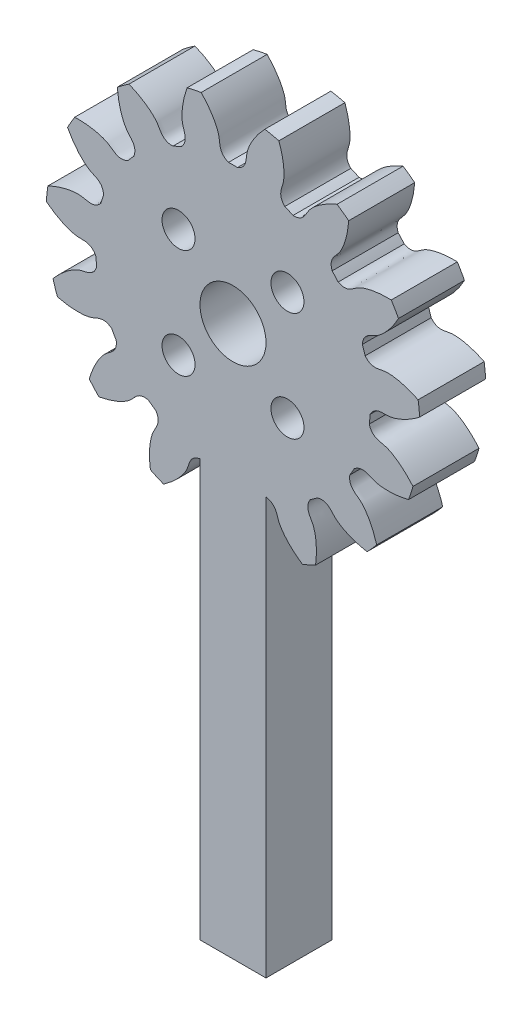
SolidWorks part; units mm, degrees
ref_plane "前视基准面" through (0, 0, 0) normal (0, 0, 1) x (1, 0, 0)
ref_plane "上视基准面" through (0, 0, 0) normal (0, 1, 0) x (1, 0, 0)
ref_plane "右视基准面" through (0, 0, 0) normal (1, 0, 0) x (0, 0, -1)
sketch "草图1" plane through (0, 0, 0) normal (0, 0, 1) x (1, 0, 0)
  circle A0 centre (0, 0) radius 17
extrude "凸台-拉伸1" add sketch "草图1" along normal blind 30
ref_axis "基准轴1" through (0, 0, -1.5) along (0, 0, 1)
sketch "草图2" plane through (0, 0, 0) normal (0, 0, 1) x (1, 0, 0)
  line L0 (0, 0) -> (0, 17) construction
  circle A0 centre (0, 0) radius 17 construction
  arc A1 (0.4086, 12.4933) -> (-0.4086, 12.4933) centre (0, 0) ccw
  arc A2 (6.4937, 19.2719) -> (-6.4937, 19.2719) centre (0, 0) ccw
  spline S0 degree 3 poles (0.4086, 12.4933) (1.3144, 12.8688) (1.1442, 13.5727) (1.3025, 14.217) (1.3149, 14.2633) (1.3297, 14.3148) (1.3472, 14.3713) (1.3676, 14.4329) (1.3912, 14.4993) (1.418, 14.5705) (1.4484, 14.6465) (1.4824, 14.7269) (1.5204, 14.8119) (1.5624, 14.9011) (1.6088, 14.9946) (1.6596, 15.0921) (1.715, 15.1935) (1.7753, 15.2987) (1.8405, 15.4075) (1.9109, 15.5198) (1.9867, 15.6353) (2.0679, 15.754) (2.1547, 15.8755) (2.2473, 15.9999) (2.3459, 16.1268) (2.4505, 16.2561) (2.5613, 16.3877) (2.6784, 16.5212) (2.802, 16.6565) (2.9322, 16.7934) (3.069, 16.9316) (3.2126, 17.0711) (3.3631, 17.2115) (3.5206, 17.3526) (3.6851, 17.4942) (3.8568, 17.6361) (4.0357, 17.778) (4.2219, 17.9197) (4.4154, 18.061) (4.6163, 18.2017) (4.8247, 18.3414) (5.0406, 18.48) (5.2641, 18.6172) (5.4951, 18.7527) (5.7336, 18.8864) (6.0652, 19.0635) (6.3203, 19.1901) (6.4937, 19.2719) knots 0 0 0 0 0.202473 0.206979 0.212085 0.217793 0.224101 0.23101 0.23852 0.24663 0.255341 0.264653 0.274566 0.285079 0.296194 0.307909 0.320225 0.333141 0.346659 0.360777 0.375496 0.390816 0.406736 0.423257 0.440379 0.458102 0.476426 0.49535 0.514875 0.535001 0.555728 0.577055 0.598984 0.621513 0.644642 0.668373 0.692704 0.717636 0.743169 0.769303 0.796037 0.823373 0.851309 0.879845 0.908983 0.938721 1 1 1 1
  spline S1 degree 3 poles (-0.4086, 12.4933) (-1.3144, 12.8688) (-1.1442, 13.5727) (-1.3025, 14.217) (-1.3149, 14.2633) (-1.3297, 14.3148) (-1.3472, 14.3713) (-1.3676, 14.4329) (-1.3912, 14.4993) (-1.418, 14.5705) (-1.4484, 14.6465) (-1.4824, 14.7269) (-1.5204, 14.8119) (-1.5624, 14.9011) (-1.6088, 14.9946) (-1.6596, 15.0921) (-1.715, 15.1935) (-1.7753, 15.2987) (-1.8405, 15.4075) (-1.9109, 15.5198) (-1.9867, 15.6353) (-2.0679, 15.754) (-2.1547, 15.8755) (-2.2473, 15.9999) (-2.3459, 16.1268) (-2.4505, 16.2561) (-2.5613, 16.3877) (-2.6784, 16.5212) (-2.802, 16.6565) (-2.9322, 16.7934) (-3.069, 16.9316) (-3.2126, 17.0711) (-3.3631, 17.2115) (-3.5206, 17.3526) (-3.6851, 17.4942) (-3.8568, 17.6361) (-4.0357, 17.778) (-4.2219, 17.9197) (-4.4154, 18.061) (-4.6163, 18.2017) (-4.8247, 18.3414) (-5.0406, 18.48) (-5.2641, 18.6172) (-5.4951, 18.7527) (-5.7336, 18.8864) (-6.0652, 19.0635) (-6.3203, 19.1901) (-6.4937, 19.2719) knots 0 0 0 0 0.202473 0.206979 0.212085 0.217793 0.224101 0.23101 0.23852 0.24663 0.255341 0.264653 0.274566 0.285079 0.296194 0.307909 0.320225 0.333141 0.346659 0.360777 0.375496 0.390816 0.406736 0.423257 0.440379 0.458102 0.476426 0.49535 0.514875 0.535001 0.555728 0.577055 0.598984 0.621513 0.644642 0.668373 0.692704 0.717636 0.743169 0.769303 0.796037 0.823373 0.851309 0.879845 0.908983 0.938721 1 1 1 1
extrude "切除-拉伸1" cut sketch "草图2" along normal through all
pattern_circular "阵列(圆周)1" count 15 every 24 about axis through (0, 0, -1.5) along (0, 0, 1) of "切除-拉伸1"
sketch "草图3" plane through (0, 0, 0) normal (0, 0, 1) x (1, 0, 0)
  circle A0 centre (0, 0) radius 15 construction
  dimension "Dn" = 30
sketch "草图4" plane through (0, 0, 30) normal (0, 0, 1) x (1, 0, 0)
  arc A30 (-4.7082, 11.5794) -> (-5.4547, 11.247) centre (0, 0) ccw
  arc A31 (-9.4567, 14.127) -> (-10.5132, 13.3593) centre (0, 0) ccw
  arc A32 (-9.011, 8.6633) -> (-9.5577, 8.056) centre (0, 0) ccw
  arc A33 (-14.3851, 9.0592) -> (-15.0381, 7.9282) centre (0, 0) ccw
  arc A34 (-11.7556, 4.2492) -> (-12.0081, 3.4721) centre (0, 0) ccw
  arc A35 (-16.8261, 2.4251) -> (-16.9627, 1.1263) centre (0, 0) ccw
  arc A36 (-12.4676, -0.8996) -> (-12.3822, -1.7122) centre (0, 0) ccw
  arc A37 (-16.3578, -4.6284) -> (-15.9542, -5.8704) centre (0, 0) ccw
  arc A38 (-11.0238, -5.8928) -> (-10.6152, -6.6005) centre (0, 0) ccw
  arc A39 (-13.0611, -10.8816) -> (-12.1872, -11.8521) centre (0, 0) ccw
  arc A40 (-7.6739, -9.8672) -> (-7.0128, -10.3475) centre (0, 0) ccw
  arc A41 (-7.5059, -15.2532) -> (-6.3129, -15.7844) centre (0, 0) ccw
  arc A42 (-2.9971, -12.1354) -> (-2.1979, -12.3053) centre (0, 0) ccw
  arc A43 (-0.653, -16.9875) -> (0.653, -16.9875) centre (0, 0) ccw
  arc A44 (2.1979, -12.3053) -> (2.9971, -12.1354) centre (0, 0) ccw
  arc A45 (6.3129, -15.7844) -> (7.5059, -15.2532) centre (0, 0) ccw
  arc A46 (7.0128, -10.3475) -> (7.6739, -9.8672) centre (0, 0) ccw
  arc A47 (12.1872, -11.8521) -> (13.0611, -10.8816) centre (0, 0) ccw
  arc A48 (10.6152, -6.6005) -> (11.0238, -5.8928) centre (0, 0) ccw
  arc A49 (15.9542, -5.8704) -> (16.3578, -4.6284) centre (0, 0) ccw
  arc A50 (12.3822, -1.7122) -> (12.4676, -0.8996) centre (0, 0) ccw
  arc A51 (16.9627, 1.1263) -> (16.8261, 2.4251) centre (0, 0) ccw
  arc A52 (12.0081, 3.4721) -> (11.7556, 4.2492) centre (0, 0) ccw
  arc A53 (15.0381, 7.9282) -> (14.3851, 9.0592) centre (0, 0) ccw
  arc A54 (9.5577, 8.056) -> (9.011, 8.6633) centre (0, 0) ccw
  arc A55 (10.5132, 13.3593) -> (9.4567, 14.127) centre (0, 0) ccw
  arc A56 (5.4547, 11.247) -> (4.7082, 11.5794) centre (0, 0) ccw
  arc A57 (4.1706, 16.4805) -> (2.8932, 16.752) centre (0, 0) ccw
  arc A58 (0.4086, 12.4933) -> (-0.4086, 12.4933) centre (0, 0) ccw
  arc A59 (-2.8932, 16.752) -> (-4.1706, 16.4805) centre (0, 0) ccw
  arc A60 (-4.7082, 11.5794) -> (-5.4547, 11.247) centre (0, 0) ccw
  arc A61 (-9.4567, 14.127) -> (-10.5132, 13.3593) centre (0, 0) ccw
  arc A62 (-9.011, 8.6633) -> (-9.5577, 8.056) centre (0, 0) ccw
  arc A63 (-14.3851, 9.0592) -> (-15.0381, 7.9282) centre (0, 0) ccw
  arc A64 (-11.7556, 4.2492) -> (-12.0081, 3.4721) centre (0, 0) ccw
  arc A65 (-16.8261, 2.4251) -> (-16.9627, 1.1263) centre (0, 0) ccw
  arc A66 (-12.4676, -0.8996) -> (-12.3822, -1.7122) centre (0, 0) ccw
  arc A67 (-16.3578, -4.6284) -> (-15.9542, -5.8704) centre (0, 0) ccw
  arc A68 (-11.0238, -5.8928) -> (-10.6152, -6.6005) centre (0, 0) ccw
  arc A69 (-13.0611, -10.8816) -> (-12.1872, -11.8521) centre (0, 0) ccw
  arc A70 (-7.6739, -9.8672) -> (-7.0128, -10.3475) centre (0, 0) ccw
  arc A71 (-7.5059, -15.2532) -> (-6.3129, -15.7844) centre (0, 0) ccw
  arc A72 (-2.9971, -12.1354) -> (-2.1979, -12.3053) centre (0, 0) ccw
  arc A73 (-0.653, -16.9875) -> (0.653, -16.9875) centre (0, 0) ccw
  arc A74 (2.1979, -12.3053) -> (2.9971, -12.1354) centre (0, 0) ccw
  arc A75 (6.3129, -15.7844) -> (7.5059, -15.2532) centre (0, 0) ccw
  arc A76 (7.0128, -10.3475) -> (7.6739, -9.8672) centre (0, 0) ccw
  arc A77 (12.1872, -11.8521) -> (13.0611, -10.8816) centre (0, 0) ccw
  arc A78 (10.6152, -6.6005) -> (11.0238, -5.8928) centre (0, 0) ccw
  arc A79 (15.9542, -5.8704) -> (16.3578, -4.6284) centre (0, 0) ccw
  arc A80 (12.3822, -1.7122) -> (12.4676, -0.8996) centre (0, 0) ccw
  arc A81 (16.9627, 1.1263) -> (16.8261, 2.4251) centre (0, 0) ccw
  arc A82 (12.0081, 3.4721) -> (11.7556, 4.2492) centre (0, 0) ccw
  arc A83 (15.0381, 7.9282) -> (14.3851, 9.0592) centre (0, 0) ccw
  arc A84 (9.5577, 8.056) -> (9.011, 8.6633) centre (0, 0) ccw
  arc A85 (10.5132, 13.3593) -> (9.4567, 14.127) centre (0, 0) ccw
  arc A86 (5.4547, 11.247) -> (4.7082, 11.5794) centre (0, 0) ccw
  arc A87 (4.1706, 16.4805) -> (2.8932, 16.752) centre (0, 0) ccw
  arc A88 (0.4086, 12.4933) -> (-0.4086, 12.4933) centre (0, 0) ccw
  arc A89 (-2.8932, 16.752) -> (-4.1706, 16.4805) centre (0, 0) ccw
  spline S30 degree 3 poles (3089.1595, 2545.0128) (-48.0651, -41.2526) (-1.4026, 5.2781) (-6.9834, 12.4722) (-7.0266, 12.5244) (-7.0761, 12.5809) (-7.1369, 12.6476) (-7.2252, 12.7386) (-7.3478, 12.8552) (-7.4919, 12.9818) (-7.6584, 13.1167) (-7.8482, 13.2583) (-8.0622, 13.405) (-8.3009, 13.555) (-8.565, 13.7067) (-8.8549, 13.858) (-42.0056, 29.516) (-165.8302, -157.3856) (3462.6996, 1998.8009) knots -2.221696 -2.221696 -2.221696 -2.221696 0.673329 0.677835 0.688649 0.694957 0.701866 0.717486 0.735509 0.755935 0.778765 0.803997 0.831633 0.861672 0.894113 0.928958 0.966206 12.611489 12.611489 12.611489 12.611489 only from (-5.4547, 11.247) to (-9.4567, 14.127)
  spline S31 degree 3 poles (-2967.0957, -2679.8675) (198.3354, 111.6925) (-15.6965, 48.1718) (-10.4174, 12.5396) (-10.3587, 12.2293) (-10.2927, 11.9436) (-10.2213, 11.6825) (-10.1464, 11.4459) (-10.0697, 11.2338) (-10.0041, 11.0727) (-9.9413, 10.931) (-9.8926, 10.8293) (-9.8442, 10.7358) (-9.8106, 10.6738) (-9.7785, 10.6175) (-9.74, 10.5529) (-9.7038, 10.4958) (-4.5863, 2.965) (54.0858, 32.9645) (-3374.9897, -2151.4722) knots -11.389987 -11.389987 -11.389987 -11.389987 0.052718 0.088765 0.122408 0.153648 0.182485 0.208919 0.23295 0.254578 0.264491 0.282514 0.290624 0.298134 0.305043 0.311351 0.322165 0.326671 3.221678 3.221678 3.221678 3.221678 only from (-10.5132, 13.3593) to (-9.011, 8.6633)
  spline S32 degree 3 poles (1786.9376, 3581.4592) (-27.1307, -57.236) (-3.4282, 4.2513) (-11.4526, 8.5535) (-11.5132, 8.5836) (-11.5815, 8.6151) (-11.6641, 8.6513) (-11.7819, 8.6985) (-11.9413, 8.7552) (-12.1243, 8.8122) (-12.3313, 8.8677) (-12.5623, 8.9199) (-12.8175, 8.9669) (-13.0966, 9.0069) (-13.3995, 9.038) (-13.7259, 9.0583) (-50.3793, 9.879) (-87.479, -211.2281) (2350.348, 3234.4023) knots -2.221696 -2.221696 -2.221696 -2.221696 0.673329 0.677835 0.688649 0.694957 0.701866 0.717486 0.735509 0.755935 0.778765 0.803997 0.831633 0.861672 0.894113 0.928958 0.966206 12.611489 12.611489 12.611489 12.611489 only from (-9.5577, 8.056) to (-14.3851, 9.0592)
  spline S33 degree 3 poles (-1620.5765, -3655.0073) (135.759, 182.7064) (-33.9327, 37.6228) (-14.6171, 7.2183) (-14.4372, 6.9587) (-14.2607, 6.7246) (-14.0893, 6.5151) (-13.9246, 6.3295) (-13.7683, 6.1669) (-13.6429, 6.0464) (-13.5278, 5.9425) (-13.442, 5.8694) (-13.3598, 5.8036) (-13.3039, 5.7607) (-13.2516, 5.7223) (-13.1902, 5.6789) (-13.1339, 5.6415) (-5.3958, 0.8433) (36.002, 52.1132) (-2208.1239, -3338.1997) knots -11.389987 -11.389987 -11.389987 -11.389987 0.052718 0.088765 0.122408 0.153648 0.182485 0.208919 0.23295 0.254578 0.264491 0.282514 0.290624 0.298134 0.305043 0.311351 0.322165 0.326671 3.221678 3.221678 3.221678 3.221678 only from (-15.0381, 7.9282) to (-11.7556, 4.2492)
  spline S34 degree 3 poles (175.7381, 3998.6388) (-1.5051, -63.3227) (-4.8609, 2.4894) (-13.9415, 3.1558) (-14.0091, 3.1587) (-14.0843, 3.1597) (-14.1745, 3.1591) (-14.3013, 3.1544) (-14.47, 3.1414) (-14.6604, 3.119) (-14.872, 3.0855) (-15.1043, 3.0392) (-15.3565, 2.9783) (-15.6277, 2.9013) (-15.9171, 2.8065) (-16.2236, 2.6924) (-50.0419, -11.4661) (5.9982, -228.5474) (831.5998, 3910.7461) knots -2.221696 -2.221696 -2.221696 -2.221696 0.673329 0.677835 0.688649 0.694957 0.701866 0.717486 0.735509 0.755935 0.778765 0.803997 0.831633 0.861672 0.894113 0.928958 0.966206 12.611489 12.611489 12.611489 12.611489 only from (-12.0081, 3.4721) to (-16.8261, 2.4251)
  spline S35 degree 3 poles (6.1551, -3998.1632) (49.7086, 222.1288) (-46.3016, 20.5684) (-16.2893, 0.649) (-16.0194, 0.485) (-15.763, 0.3428) (-15.5212, 0.2212) (-15.2952, 0.1186) (-15.0863, 0.0336) (-14.9227, -0.0254) (-14.7753, -0.0735) (-14.6671, -0.1054) (-14.5653, -0.132) (-14.4968, -0.1485) (-14.4334, -0.1624) (-14.3597, -0.177) (-14.293, -0.1883) (-5.2723, -1.4243) (11.6931, 62.2511) (-659.4535, -3947.7221) knots -11.389987 -11.389987 -11.389987 -11.389987 0.052718 0.088765 0.122408 0.153648 0.182485 0.208919 0.23295 0.254578 0.264491 0.282514 0.290624 0.298134 0.305043 0.311351 0.322165 0.326671 3.221678 3.221678 3.221678 3.221678 only from (-16.9627, 1.1263) to (-12.4676, -0.8996)
  spline S36 degree 3 poles (-1465.8482, 3724.4174) (24.3807, -58.4604) (-5.4532, 0.297) (-14.0198, -2.7875) (-14.0827, -2.8124) (-14.1518, -2.8421) (-14.234, -2.8793) (-14.3479, -2.9352) (-14.4967, -3.0157) (-14.6615, -3.1136) (-14.8413, -3.2303) (-15.0346, -3.3671) (-15.2402, -3.5252) (-15.4567, -3.7059) (-15.6825, -3.9102) (-15.9161, -4.1391) (-41.0519, -30.8287) (98.4382, -206.3487) (-830.9396, 3910.8865) knots -2.221696 -2.221696 -2.221696 -2.221696 0.673329 0.677835 0.688649 0.694957 0.701866 0.717486 0.735509 0.755935 0.778765 0.803997 0.831633 0.861672 0.894113 0.928958 0.966206 12.611489 12.611489 12.611489 12.611489 only from (-12.3822, -1.7122) to (-16.3578, -4.6284)
  spline S37 degree 3 poles (1631.8224, -3650.0003) (-44.9369, 223.143) (-50.6646, -0.0424) (-15.145, -6.0326) (-14.8318, -6.0726) (-14.5396, -6.0982) (-14.2692, -6.111) (-14.0211, -6.1128) (-13.7957, -6.1054) (-13.6222, -6.0928) (-13.468, -6.0768) (-13.3562, -6.062) (-13.2524, -6.0449) (-13.1831, -6.032) (-13.1196, -6.0189) (-13.0462, -6.0023) (-12.9807, -5.9855) (-4.2372, -3.4456) (-14.6376, 61.6252) (1003.2425, -3874.6475) knots -11.389987 -11.389987 -11.389987 -11.389987 0.052718 0.088765 0.122408 0.153648 0.182485 0.208919 0.23295 0.254578 0.264491 0.282514 0.290624 0.298134 0.305043 0.311351 0.322165 0.326671 3.221678 3.221678 3.221678 3.221678 only from (-15.9542, -5.8704) to (-11.0238, -5.8928)
  spline S38 degree 3 poles (-2853.976, 2806.2104) (46.0508, -43.4897) (-5.1025, -1.9467) (-11.6739, -8.2489) (-11.7213, -8.2972) (-11.7723, -8.3524) (-11.8323, -8.4198) (-11.9136, -8.5172) (-12.0168, -8.6513) (-12.1276, -8.8078) (-12.2443, -8.9875) (-12.3653, -9.1911) (-12.4888, -9.4192) (-12.6131, -9.6723) (-12.7363, -9.9508) (-12.8565, -10.255) (-24.9636, -44.8607) (173.8574, -148.4705) (-2349.8019, 3234.799) knots -2.221696 -2.221696 -2.221696 -2.221696 0.673329 0.677835 0.688649 0.694957 0.701866 0.717486 0.735509 0.755935 0.778765 0.803997 0.831633 0.861672 0.894113 0.928958 0.966206 12.611489 12.611489 12.611489 12.611489 only from (-10.6152, -6.6005) to (-13.0611, -10.8816)
  spline S39 degree 3 poles (2975.3328, -2670.7192) (-131.8123, 185.5738) (-46.2672, -20.6458) (-11.382, -11.6711) (-11.0795, -11.5803) (-10.8023, -11.4848) (-10.5501, -11.3865) (-10.3226, -11.2872) (-10.1197, -11.1888) (-9.9664, -11.1067) (-9.832, -11.0294) (-9.7359, -10.9703) (-9.648, -10.9125) (-9.5899, -10.8726) (-9.5372, -10.8348) (-9.477, -10.7898) (-9.4239, -10.7477) (-2.4694, -4.8712) (-38.4374, 50.3438) (2492.4687, -3131.6111) knots -11.389987 -11.389987 -11.389987 -11.389987 0.052718 0.088765 0.122408 0.153648 0.182485 0.208919 0.23295 0.254578 0.264491 0.282514 0.290624 0.298134 0.305043 0.311351 0.322165 0.326671 3.221678 3.221678 3.221678 3.221678 only from (-12.1872, -11.8521) to (-7.6739, -9.8672)
  spline S40 degree 3 poles (-3748.6254, 1402.7842) (59.7584, -20.9993) (-3.8696, -3.8538) (-7.3095, -12.2839) (-7.3331, -12.3474) (-7.3573, -12.4185) (-7.3847, -12.5045) (-7.4193, -12.6266) (-7.4591, -12.791) (-7.4966, -12.979) (-7.5302, -13.1907) (-7.5579, -13.4259) (-7.578, -13.6845) (-7.5886, -13.9663) (-7.5878, -14.2708) (-7.574, -14.5976) (-4.5589, -51.1359) (219.215, -64.9204) (-3462.3621, 1999.3854) knots -2.221696 -2.221696 -2.221696 -2.221696 0.673329 0.677835 0.688649 0.694957 0.701866 0.717486 0.735509 0.755935 0.778765 0.803997 0.831633 0.861672 0.894113 0.928958 0.966206 12.611489 12.611489 12.611489 12.611489 only from (-7.0128, -10.3475) to (-7.5059, -15.2532)
  spline S41 degree 3 poles (3804.3812, -1229.6465) (-195.8962, 115.9172) (-33.8697, -37.6795) (-5.6509, -15.2915) (-5.4115, -15.0855) (-5.1971, -14.8855) (-5.0067, -14.6931) (-4.8393, -14.51) (-4.6939, -14.3375) (-4.5872, -14.2002) (-4.4959, -14.0749) (-4.4321, -13.9819) (-4.3754, -13.8932) (-4.3385, -13.8331) (-4.3057, -13.7772) (-4.2691, -13.7116) (-4.2377, -13.6516) (-0.2746, -5.4544) (-55.591, 30.3574) (3550.7245, -1847.0907) knots -11.389987 -11.389987 -11.389987 -11.389987 0.052718 0.088765 0.122408 0.153648 0.182485 0.208919 0.23295 0.254578 0.264491 0.282514 0.290624 0.298134 0.305043 0.311351 0.322165 0.326671 3.221678 3.221678 3.221678 3.221678 only from (-6.3129, -15.7844) to (-2.9971, -12.1354)
  spline S42 degree 3 poles (-3995.1035, -243.1962) (63.1332, 5.1221) (-1.9676, -5.0945) (-1.6813, -14.195) (-1.677, -14.2625) (-1.6702, -14.3374) (-1.6602, -14.4271) (-1.6422, -14.5527) (-1.6116, -14.719) (-1.5695, -14.9061) (-1.514, -15.1131) (-1.4437, -15.3393) (-1.3568, -15.5837) (-1.2519, -15.8454) (-1.1274, -16.1233) (-0.9818, -16.4162) (16.6341, -48.5692) (226.6684, 29.855) (-3976.2485, 418.2599) knots -2.221696 -2.221696 -2.221696 -2.221696 0.673329 0.677835 0.688649 0.694957 0.701866 0.717486 0.735509 0.755935 0.778765 0.803997 0.831633 0.861672 0.894113 0.928958 0.966206 12.611489 12.611489 12.611489 12.611489 only from (-2.1979, -12.3053) to (-0.653, -16.9875)
  spline S43 degree 3 poles (3975.6174, 424.0432) (-226.1079, 26.2175) (-15.6159, -48.198) (1.0573, -16.2679) (1.1922, -15.9824) (1.3067, -15.7124) (1.4024, -15.4592) (1.4808, -15.2238) (1.5435, -15.0071) (1.5851, -14.8383) (1.6176, -14.6867) (1.638, -14.5758) (1.6538, -14.4717) (1.663, -14.4018) (1.6702, -14.3374) (1.677, -14.2625) (1.6813, -14.195) (1.9676, -5.0946) (-63.1324, 5.122) (3995.0277, -243.1916) knots -11.389987 -11.389987 -11.389987 -11.389987 0.052718 0.088765 0.122408 0.153648 0.182485 0.208919 0.23295 0.254578 0.264491 0.282514 0.290624 0.298134 0.305043 0.311351 0.322165 0.326671 3.221678 3.221678 3.221678 3.221678 only from (0.653, -16.9875) to (2.1979, -12.3053)
  spline S44 degree 3 poles (-3550.7918, -1847.1258) (55.5917, 30.3579) (0.2746, -5.4544) (4.2377, -13.6516) (4.2691, -13.7116) (4.3057, -13.7772) (4.3513, -13.855) (4.4189, -13.9625) (4.5145, -14.102) (4.6291, -14.2557) (4.7639, -14.4223) (4.9202, -14.6003) (5.0989, -14.7883) (5.3012, -14.9847) (5.528, -15.1879) (5.7802, -15.3963) (34.9509, -37.6045) (194.9288, 119.4683) (-3802.6054, -1235.1865) knots -2.221696 -2.221696 -2.221696 -2.221696 0.673329 0.677835 0.688649 0.694957 0.701866 0.717486 0.735509 0.755935 0.778765 0.803997 0.831633 0.861672 0.894113 0.928958 0.966206 12.611489 12.611489 12.611489 12.611489 only from (2.9971, -12.1354) to (6.3129, -15.7844)
  spline S45 degree 3 poles (3459.4333, 2004.4121) (-217.2235, -68.0155) (5.338, -50.3826) (7.5826, -14.4315) (7.5897, -14.1157) (7.5846, -13.8225) (7.569, -13.5523) (7.5449, -13.3054) (7.514, -13.0819) (7.4834, -12.9107) (7.4513, -12.759) (7.4249, -12.6494) (7.397, -12.5479) (7.377, -12.4803) (7.3573, -12.4185) (7.3331, -12.3474) (7.3095, -12.2839) (3.8697, -3.8538) (-59.7576, -20.999) (3748.5543, 1402.7576) knots -11.389987 -11.389987 -11.389987 -11.389987 0.052718 0.088765 0.122408 0.153648 0.182485 0.208919 0.23295 0.254578 0.264491 0.282514 0.290624 0.298134 0.305043 0.311351 0.322165 0.326671 3.221678 3.221678 3.221678 3.221678 only from (7.5059, -15.2532) to (7.0128, -10.3475)
  spline S46 degree 3 poles (-2492.516, -3131.6705) (38.4378, 50.3445) (2.4694, -4.8711) (9.4239, -10.7477) (9.477, -10.7898) (9.5372, -10.8348) (9.6105, -10.8873) (9.7159, -10.958) (9.86, -11.0466) (10.0272, -11.1405) (10.2181, -11.2378) (10.4333, -11.3368) (10.673, -11.4358) (10.9377, -11.533) (11.2276, -11.6264) (11.5427, -11.7142) (47.2244, -20.1376) (129.4842, 188.4244) (-2971.4573, -2675.058) knots -2.221696 -2.221696 -2.221696 -2.221696 0.673329 0.677835 0.688649 0.694957 0.701866 0.717486 0.735509 0.755935 0.778765 0.803997 0.831633 0.861672 0.894113 0.928958 0.966206 12.611489 12.611489 12.611489 12.611489 only from (7.6739, -9.8672) to (12.1872, -11.8521)
  spline S47 degree 3 poles (2345.0818, 3238.1998) (-170.7791, -150.488) (25.369, -43.8556) (12.7969, -10.0997) (12.6749, -9.8084) (12.551, -9.5426) (12.4269, -9.302) (12.3044, -9.0863) (12.1853, -8.8947) (12.0877, -8.7508) (11.9967, -8.6252) (11.9279, -8.5358) (11.8612, -8.4545) (11.8154, -8.4009) (11.7723, -8.3524) (11.7213, -8.2972) (11.6739, -8.2489) (5.1026, -1.9467) (-46.0502, -43.4892) (2853.9219, 2806.1572) knots -11.389987 -11.389987 -11.389987 -11.389987 0.052718 0.088765 0.122408 0.153648 0.182485 0.208919 0.23295 0.254578 0.264491 0.282514 0.290624 0.298134 0.305043 0.311351 0.322165 0.326671 3.221678 3.221678 3.221678 3.221678 only from (13.0611, -10.8816) to (10.6152, -6.6005)
  spline S48 degree 3 poles (-1003.2615, -3874.721) (14.6378, 61.626) (4.2371, -3.4456) (12.9807, -5.9855) (13.0462, -6.0023) (13.1196, -6.0189) (13.2079, -6.0371) (13.3329, -6.0589) (13.5006, -6.0812) (13.6915, -6.0989) (13.9055, -6.1101) (14.1424, -6.1131) (14.4017, -6.106) (14.683, -6.0871) (14.9858, -6.0545) (15.3093, -6.0066) (51.3323, 0.8113) (41.6506, 224.8002) (-1626.5172, -3652.3876) knots -2.221696 -2.221696 -2.221696 -2.221696 0.673329 0.677835 0.688649 0.694957 0.701866 0.717486 0.735509 0.755935 0.778765 0.803997 0.831633 0.861672 0.894113 0.928958 0.966206 12.611489 12.611489 12.611489 12.611489 only from (11.0238, -5.8928) to (15.9542, -5.8704)
  spline S49 degree 3 poles (825.2443, 3912.0734) (-94.8055, -206.9397) (41.0134, -29.7456) (15.7984, -4.0215) (15.5686, -3.805) (15.3472, -3.6127) (15.136, -3.4434) (14.9363, -3.2961) (14.7496, -3.1695) (14.6019, -3.0778) (14.4677, -3) (14.3685, -2.9464) (14.2745, -2.8991) (14.2109, -2.8688) (14.1518, -2.8421) (14.0827, -2.8124) (14.0198, -2.7875) (5.4532, 0.297) (-24.3803, -58.4597) (1465.8204, 3724.3468) knots -11.389987 -11.389987 -11.389987 -11.389987 0.052718 0.088765 0.122408 0.153648 0.182485 0.208919 0.23295 0.254578 0.264491 0.282514 0.290624 0.298134 0.305043 0.311351 0.322165 0.326671 3.221678 3.221678 3.221678 3.221678 only from (16.3578, -4.6284) to (12.3822, -1.7122)
  spline S50 degree 3 poles (659.466, -3947.797) (-11.6933, 62.2519) (5.2723, -1.4243) (14.293, -0.1883) (14.3597, -0.177) (14.4334, -0.1624) (14.5216, -0.1431) (14.6446, -0.1121) (14.8069, -0.0642) (14.9885, -0.0027) (15.1886, 0.074) (15.4061, 0.1676) (15.6401, 0.2795) (15.8894, 0.4113) (16.1528, 0.5642) (16.4289, 0.7396) (46.5644, 21.6199) (-53.3848, 222.306) (-0.3375, -3998.1863) knots -2.221696 -2.221696 -2.221696 -2.221696 0.673329 0.677835 0.688649 0.694957 0.701866 0.717486 0.735509 0.755935 0.778765 0.803997 0.831633 0.861672 0.894113 0.928958 0.966206 12.611489 12.611489 12.611489 12.611489 only from (12.4676, -0.8996) to (16.9627, 1.1263)
  spline S51 degree 3 poles (-837.2855, 3909.514) (-2.4392, -227.6097) (49.5662, -10.4923) (16.0683, 2.752) (15.7702, 2.8562) (15.4898, 2.942) (15.228, 3.0107) (14.9856, 3.064) (14.7636, 3.1037) (14.5913, 3.1275) (14.4372, 3.1439) (14.3247, 3.1526) (14.2196, 3.1574) (14.1491, 3.1593) (14.0843, 3.1597) (14.0091, 3.1587) (13.9415, 3.1558) (4.861, 2.4894) (1.5052, -63.3219) (-175.7348, 3998.563) knots -11.389987 -11.389987 -11.389987 -11.389987 0.052718 0.088765 0.122408 0.153648 0.182485 0.208919 0.23295 0.254578 0.264491 0.282514 0.290624 0.298134 0.305043 0.311351 0.322165 0.326671 3.221678 3.221678 3.221678 3.221678 only from (16.8261, 2.4251) to (12.0081, 3.4721)
  spline S52 degree 3 poles (2208.1658, -3338.263) (-36.0025, 52.1139) (5.3958, 0.8432) (13.1339, 5.6415) (13.1902, 5.6789) (13.2516, 5.7223) (13.3243, 5.7758) (13.4241, 5.8541) (13.5529, 5.9638) (13.6938, 6.0939) (13.8453, 6.2454) (14.006, 6.4194) (14.1743, 6.6168) (14.3485, 6.8385) (14.5269, 7.0853) (14.7077, 7.3578) (33.7451, 38.6902) (-139.1894, 181.3731) (1625.9006, -3652.6622) knots -2.221696 -2.221696 -2.221696 -2.221696 0.673329 0.677835 0.688649 0.694957 0.701866 0.717486 0.735509 0.755935 0.778765 0.803997 0.831633 0.861672 0.894113 0.928958 0.966206 12.611489 12.611489 12.611489 12.611489 only from (11.7556, 4.2492) to (15.0381, 7.9282)
  spline S53 degree 3 poles (-2355.0409, 3230.9641) (90.3489, -208.9239) (49.5486, 10.5752) (13.5598, 9.0496) (13.2451, 9.0236) (12.954, 8.9879) (12.6869, 8.9442) (12.4438, 8.8943) (12.2248, 8.8403) (12.0578, 8.7919) (11.9103, 8.7442) (11.804, 8.7064) (11.706, 8.6681) (11.6409, 8.6411) (11.5815, 8.6151) (11.5132, 8.5836) (11.4526, 8.5535) (3.4282, 4.2513) (27.1304, -57.2352) (-1786.9038, 3581.3913) knots -11.389987 -11.389987 -11.389987 -11.389987 0.052718 0.088765 0.122408 0.153648 0.182485 0.208919 0.23295 0.254578 0.264491 0.282514 0.290624 0.298134 0.305043 0.311351 0.322165 0.326671 3.221678 3.221678 3.221678 3.221678 only from (14.3851, 9.0592) to (9.5577, 8.056)
  spline S54 degree 3 poles (3375.0538, -2151.513) (-54.0865, 32.9648) (4.5863, 2.965) (9.7038, 10.4958) (9.74, 10.5529) (9.7785, 10.6175) (9.8231, 10.6959) (9.8824, 10.8081) (9.9555, 10.9607) (10.0313, 11.1368) (10.1081, 11.3368) (10.1842, 11.5611) (10.2576, 11.8099) (10.3265, 12.0833) (10.3891, 12.3814) (10.4435, 12.7039) (15.091, 49.0706) (-200.9269, 109.0791) (2971.0056, -2675.5596) knots -2.221696 -2.221696 -2.221696 -2.221696 0.673329 0.677835 0.688649 0.694957 0.701866 0.717486 0.735509 0.755935 0.778765 0.803997 0.831633 0.861672 0.894113 0.928958 0.966206 12.611489 12.611489 12.611489 12.611489 only from (9.011, 8.6633) to (10.5132, 13.3593)
  spline S55 degree 3 poles (-3465.5884, 1993.7511) (167.5149, -154.1133) (40.9636, 29.8142) (8.7067, 13.7825) (8.4297, 13.6308) (8.1784, 13.4797) (7.9521, 13.3311) (7.7503, 13.1867) (7.5723, 13.0483) (7.4394, 12.9362) (7.324, 12.8326) (7.2423, 12.7548) (7.1683, 12.6799) (7.1198, 12.6288) (7.0761, 12.5809) (7.0266, 12.5244) (6.9834, 12.4722) (1.4027, 5.2781) (48.0645, -41.2521) (-3089.1009, 2544.9645) knots -11.389987 -11.389987 -11.389987 -11.389987 0.052718 0.088765 0.122408 0.153648 0.182485 0.208919 0.23295 0.254578 0.264491 0.282514 0.290624 0.298134 0.305043 0.311351 0.322165 0.326671 3.221678 3.221678 3.221678 3.221678 only from (9.4567, 14.127) to (5.4547, 11.247)
  spline S56 degree 3 poles (3958.3642, -592.7469) (-62.8185, 8.1159) (2.9838, 4.5741) (4.5958, 13.5352) (4.6057, 13.6022) (4.6146, 13.6768) (4.6235, 13.7666) (4.632, 13.8932) (4.6367, 14.0623) (4.6343, 14.254) (4.6231, 14.468) (4.6014, 14.7039) (4.5672, 14.961) (4.519, 15.2388) (4.4549, 15.5366) (4.3734, 15.8533) (-6.1725, 50.9663) (-227.9224, 17.9244) (3802.3968, -1235.8285) knots -2.221696 -2.221696 -2.221696 -2.221696 0.673329 0.677835 0.688649 0.694957 0.701866 0.717486 0.735509 0.755935 0.778765 0.803997 0.831633 0.861672 0.894113 0.928958 0.966206 12.611489 12.611489 12.611489 12.611489 only from (4.7082, 11.5794) to (4.1706, 16.4805)
  spline S57 degree 3 poles (-3976.9042, 411.8005) (215.716, -72.6551) (25.2956, 43.898) (2.3481, 16.1323) (2.1568, 15.881) (1.9886, 15.6408) (1.8424, 15.413) (1.7167, 15.199) (1.6104, 15.0001) (1.5346, 14.8436) (1.4713, 14.7021) (1.4283, 14.5978) (1.3912, 14.4993) (1.3676, 14.4329) (1.3472, 14.3713) (1.325, 14.2995) (1.3068, 14.2343) (-0.8654, 5.3923) (60.6878, -18.136) (-3857.1644, 1068.4902) knots -11.389987 -11.389987 -11.389987 -11.389987 0.052718 0.088765 0.122408 0.153648 0.182485 0.208919 0.23295 0.254578 0.264491 0.282514 0.290624 0.298134 0.305043 0.311351 0.322165 0.326671 3.221678 3.221678 3.221678 3.221678 only from (2.8932, 16.752) to (0.4086, 12.4933)
  spline S58 degree 3 poles (3857.2375, 1068.5105) (-60.6886, -18.1363) (0.8654, 5.3923) (-1.3068, 14.2343) (-1.325, 14.2995) (-1.3472, 14.3713) (-1.3756, 14.457) (-1.4193, 14.5761) (-1.4839, 14.7325) (-1.564, 14.9067) (-1.6612, 15.0976) (-1.7771, 15.3042) (-1.9128, 15.5252) (-2.0699, 15.7594) (-2.2495, 16.0053) (-2.4528, 16.2616) (-26.3687, 44.0495) (-215.5079, -76.3296) (3976.3191, 417.5886) knots -2.221696 -2.221696 -2.221696 -2.221696 0.673329 0.677835 0.688649 0.694957 0.701866 0.717486 0.735509 0.755935 0.778765 0.803997 0.831633 0.861672 0.894113 0.928958 0.966206 12.611489 12.611489 12.611489 12.611489 only from (-0.4086, 12.4933) to (-2.8932, 16.752)
  spline S59 degree 3 poles (-3800.5771, -1241.3542) (226.6178, 21.3659) (5.2538, 50.3915) (-4.4165, 15.6926) (-4.489, 15.3853) (-4.545, 15.0974) (-4.5859, 14.8298) (-4.6137, 14.5833) (-4.6299, 14.3583) (-4.6355, 14.1845) (-4.6358, 14.0294) (-4.6327, 13.9167) (-4.6265, 13.8116) (-4.621, 13.7414) (-4.6146, 13.6768) (-4.6057, 13.6022) (-4.5958, 13.5352) (-2.9838, 4.5741) (62.8177, 8.1159) (-3958.2891, -592.7357) knots -11.389987 -11.389987 -11.389987 -11.389987 0.052718 0.088765 0.122408 0.153648 0.182485 0.208919 0.23295 0.254578 0.264491 0.282514 0.290624 0.298134 0.305043 0.311351 0.322165 0.326671 3.221678 3.221678 3.221678 3.221678 only from (-4.1706, 16.4805) to (-4.7082, 11.5794)
  spline S60 degree 3 poles (-5.4547, 11.247) (-6.435, 11.2216) (-6.5658, 11.9338) (-6.9834, 12.4722) (-7.0266, 12.5244) (-7.0761, 12.5809) (-7.1369, 12.6476) (-7.2252, 12.7386) (-7.3478, 12.8552) (-7.4919, 12.9818) (-7.6584, 13.1167) (-7.8482, 13.2583) (-8.0622, 13.405) (-8.3009, 13.555) (-8.565, 13.7067) (-8.8549, 13.858) (-9.1545, 13.9995) (-9.3588, 14.087) (-9.4567, 14.127) knots 0.470856 0.470856 0.470856 0.470856 0.673329 0.677835 0.688649 0.694957 0.701866 0.717486 0.735509 0.755935 0.778765 0.803997 0.831633 0.861672 0.894113 0.928958 0.966206 1 1 1 1
  spline S61 degree 3 poles (-10.5132, 13.3593) (-10.5011, 13.1949) (-10.4735, 12.9184) (-10.4174, 12.5396) (-10.3587, 12.2293) (-10.2927, 11.9436) (-10.2213, 11.6825) (-10.1464, 11.4459) (-10.0697, 11.2338) (-10.0041, 11.0727) (-9.9413, 10.931) (-9.8926, 10.8293) (-9.8442, 10.7358) (-9.8106, 10.6738) (-9.7785, 10.6175) (-9.74, 10.5529) (-9.7038, 10.4958) (-9.3208, 9.9322) (-8.6839, 9.5877) (-9.011, 8.6633) knots 0 0 0 0 0.052718 0.088765 0.122408 0.153648 0.182485 0.208919 0.23295 0.254578 0.264491 0.282514 0.290624 0.298134 0.305043 0.311351 0.322165 0.326671 0.529144 0.529144 0.529144 0.529144
  spline S62 degree 3 poles (-9.5577, 8.056) (-10.4429, 7.6341) (-10.8521, 8.2316) (-11.4526, 8.5535) (-11.5132, 8.5836) (-11.5815, 8.6151) (-11.6641, 8.6513) (-11.7819, 8.6985) (-11.9413, 8.7552) (-12.1243, 8.8122) (-12.3313, 8.8677) (-12.5623, 8.9199) (-12.8175, 8.9669) (-13.0966, 9.0069) (-13.3995, 9.038) (-13.7259, 9.0583) (-14.0572, 9.0658) (-14.2794, 9.0625) (-14.3851, 9.0592) knots 0.470856 0.470856 0.470856 0.470856 0.673329 0.677835 0.688649 0.694957 0.701866 0.717486 0.735509 0.755935 0.778765 0.803997 0.831633 0.861672 0.894113 0.928958 0.966206 1 1 1 1
  spline S63 degree 3 poles (-15.0381, 7.9282) (-14.9601, 7.7829) (-14.8225, 7.5416) (-14.6171, 7.2183) (-14.4372, 6.9587) (-14.2607, 6.7246) (-14.0893, 6.5151) (-13.9246, 6.3295) (-13.7683, 6.1669) (-13.6429, 6.0464) (-13.5278, 5.9425) (-13.442, 5.8694) (-13.3598, 5.8036) (-13.3039, 5.7607) (-13.2516, 5.7223) (-13.1902, 5.6789) (-13.1339, 5.6415) (-12.5548, 5.2824) (-11.8328, 5.2268) (-11.7556, 4.2492) knots 0 0 0 0 0.052718 0.088765 0.122408 0.153648 0.182485 0.208919 0.23295 0.254578 0.264491 0.282514 0.290624 0.298134 0.305043 0.311351 0.322165 0.326671 0.529144 0.529144 0.529144 0.529144
  spline S64 degree 3 poles (-12.0081, 3.4721) (-12.6452, 2.7266) (-13.262, 3.106) (-13.9415, 3.1558) (-14.0091, 3.1587) (-14.0843, 3.1597) (-14.1745, 3.1591) (-14.3013, 3.1544) (-14.47, 3.1414) (-14.6604, 3.119) (-14.872, 3.0855) (-15.1043, 3.0392) (-15.3565, 2.9783) (-15.6277, 2.9013) (-15.9171, 2.8065) (-16.2236, 2.6924) (-16.5292, 2.5644) (-16.731, 2.4711) (-16.8261, 2.4251) knots 0.470856 0.470856 0.470856 0.470856 0.673329 0.677835 0.688649 0.694957 0.701866 0.717486 0.735509 0.755935 0.778765 0.803997 0.831633 0.861672 0.894113 0.928958 0.966206 1 1 1 1
  spline S65 degree 3 poles (-16.9627, 1.1263) (-16.8323, 1.0252) (-16.6084, 0.8608) (-16.2893, 0.649) (-16.0194, 0.485) (-15.763, 0.3428) (-15.5212, 0.2212) (-15.2952, 0.1186) (-15.0863, 0.0336) (-14.9227, -0.0254) (-14.7753, -0.0735) (-14.6671, -0.1054) (-14.5653, -0.132) (-14.4968, -0.1485) (-14.4334, -0.1624) (-14.3597, -0.177) (-14.293, -0.1883) (-13.6179, -0.2808) (-12.9357, -0.0379) (-12.4676, -0.8996) knots 0 0 0 0 0.052718 0.088765 0.122408 0.153648 0.182485 0.208919 0.23295 0.254578 0.264491 0.282514 0.290624 0.298134 0.305043 0.311351 0.322165 0.326671 0.529144 0.529144 0.529144 0.529144
  spline S66 degree 3 poles (-12.3822, -1.7122) (-12.6609, -2.6524) (-13.3787, -2.5567) (-14.0198, -2.7875) (-14.0827, -2.8124) (-14.1518, -2.8421) (-14.234, -2.8793) (-14.3479, -2.9352) (-14.4967, -3.0157) (-14.6615, -3.1136) (-14.8413, -3.2303) (-15.0346, -3.3671) (-15.2402, -3.5252) (-15.4567, -3.7059) (-15.6825, -3.9102) (-15.9161, -4.1391) (-16.1432, -4.3803) (-16.2896, -4.5477) (-16.3578, -4.6284) knots 0.470856 0.470856 0.470856 0.470856 0.673329 0.677835 0.688649 0.694957 0.701866 0.717486 0.735509 0.755935 0.778765 0.803997 0.831633 0.861672 0.894113 0.928958 0.966206 1 1 1 1
  spline S67 degree 3 poles (-15.9542, -5.8704) (-15.7941, -5.9097) (-15.5227, -5.9689) (-15.145, -6.0326) (-14.8318, -6.0726) (-14.5396, -6.0982) (-14.2692, -6.111) (-14.0211, -6.1128) (-13.7957, -6.1054) (-13.6222, -6.0928) (-13.468, -6.0768) (-13.3562, -6.062) (-13.2524, -6.0449) (-13.1831, -6.032) (-13.1196, -6.0189) (-13.0462, -6.0023) (-12.9807, -5.9855) (-12.3264, -5.7954) (-11.8019, -5.2961) (-11.0238, -5.8928) knots 0 0 0 0 0.052718 0.088765 0.122408 0.153648 0.182485 0.208919 0.23295 0.254578 0.264491 0.282514 0.290624 0.298134 0.305043 0.311351 0.322165 0.326671 0.529144 0.529144 0.529144 0.529144
  spline S68 degree 3 poles (-10.6152, -6.6005) (-10.4875, -7.5727) (-11.1822, -7.7773) (-11.6739, -8.2489) (-11.7213, -8.2972) (-11.7723, -8.3524) (-11.8323, -8.4198) (-11.9136, -8.5172) (-12.0168, -8.6513) (-12.1276, -8.8078) (-12.2443, -8.9875) (-12.3653, -9.1911) (-12.4888, -9.4192) (-12.6131, -9.6723) (-12.7363, -9.9508) (-12.8565, -10.255) (-12.9659, -10.5677) (-13.0316, -10.7801) (-13.0611, -10.8816) knots 0.470856 0.470856 0.470856 0.470856 0.673329 0.677835 0.688649 0.694957 0.701866 0.717486 0.735509 0.755935 0.778765 0.803997 0.831633 0.861672 0.894113 0.928958 0.966206 1 1 1 1
  spline S69 degree 3 poles (-12.1872, -11.8521) (-12.0249, -11.8228) (-11.7529, -11.7665) (-11.382, -11.6711) (-11.0795, -11.5803) (-10.8023, -11.4848) (-10.5501, -11.3865) (-10.3226, -11.2872) (-10.1197, -11.1888) (-9.9664, -11.1067) (-9.832, -11.0294) (-9.7359, -10.9703) (-9.648, -10.9125) (-9.5899, -10.8726) (-9.5372, -10.8348) (-9.477, -10.7898) (-9.4239, -10.7477) (-8.9035, -10.308) (-8.6275, -9.6385) (-7.6739, -9.8672) knots 0 0 0 0 0.052718 0.088765 0.122408 0.153648 0.182485 0.208919 0.23295 0.254578 0.264491 0.282514 0.290624 0.298134 0.305043 0.311351 0.322165 0.326671 0.529144 0.529144 0.529144 0.529144
  spline S70 degree 3 poles (-7.0128, -10.3475) (-6.5007, -11.1837) (-7.0521, -11.6531) (-7.3095, -12.2839) (-7.3331, -12.3474) (-7.3573, -12.4185) (-7.3847, -12.5045) (-7.4193, -12.6266) (-7.4591, -12.791) (-7.4966, -12.979) (-7.5302, -13.1907) (-7.5579, -13.4259) (-7.578, -13.6845) (-7.5886, -13.9663) (-7.5878, -14.2708) (-7.574, -14.5976) (-7.5467, -14.9278) (-7.5203, -15.1485) (-7.5059, -15.2532) knots 0.470856 0.470856 0.470856 0.470856 0.673329 0.677835 0.688649 0.694957 0.701866 0.717486 0.735509 0.755935 0.778765 0.803997 0.831633 0.861672 0.894113 0.928958 0.966206 1 1 1 1
  spline S71 degree 3 poles (-6.3129, -15.7844) (-6.1765, -15.6917) (-5.9509, -15.5296) (-5.6509, -15.2915) (-5.4115, -15.0855) (-5.1971, -14.8855) (-5.0067, -14.6931) (-4.8393, -14.51) (-4.6939, -14.3375) (-4.5872, -14.2002) (-4.4959, -14.0749) (-4.4321, -13.9819) (-4.3754, -13.8932) (-4.3385, -13.8331) (-4.3057, -13.7772) (-4.2691, -13.7116) (-4.2377, -13.6516) (-3.9411, -13.0382) (-3.9613, -12.3143) (-2.9971, -12.1354) knots 0 0 0 0 0.052718 0.088765 0.122408 0.153648 0.182485 0.208919 0.23295 0.254578 0.264491 0.282514 0.290624 0.298134 0.305043 0.311351 0.322165 0.326671 0.529144 0.529144 0.529144 0.529144
  spline S72 degree 3 poles (-2.1979, -12.3053) (-1.3899, -12.8609) (-1.7027, -13.514) (-1.6813, -14.195) (-1.677, -14.2625) (-1.6702, -14.3374) (-1.6602, -14.4271) (-1.6422, -14.5527) (-1.6116, -14.719) (-1.5695, -14.9061) (-1.514, -15.1131) (-1.4437, -15.3393) (-1.3568, -15.5837) (-1.2519, -15.8454) (-1.1274, -16.1233) (-0.9818, -16.4162) (-0.8226, -16.7067) (-0.7087, -16.8976) (-0.653, -16.9875) knots 0.470856 0.470856 0.470856 0.470856 0.673329 0.677835 0.688649 0.694957 0.701866 0.717486 0.735509 0.755935 0.778765 0.803997 0.831633 0.861672 0.894113 0.928958 0.966206 1 1 1 1
  spline S73 degree 3 poles (0.653, -16.9875) (0.7399, -16.8473) (0.88, -16.6074) (1.0573, -16.2679) (1.1922, -15.9824) (1.3067, -15.7124) (1.4024, -15.4592) (1.4808, -15.2238) (1.5435, -15.0071) (1.5851, -14.8383) (1.6176, -14.6867) (1.638, -14.5758) (1.6538, -14.4717) (1.663, -14.4018) (1.6702, -14.3374) (1.677, -14.2625) (1.6813, -14.195) (1.7027, -13.514) (1.3899, -12.8609) (2.1979, -12.3053) knots 0 0 0 0 0.052718 0.088765 0.122408 0.153648 0.182485 0.208919 0.23295 0.254578 0.264491 0.282514 0.290624 0.298134 0.305043 0.311351 0.322165 0.326671 0.529144 0.529144 0.529144 0.529144
  spline S74 degree 3 poles (2.9971, -12.1354) (3.9613, -12.3143) (3.9411, -13.0382) (4.2377, -13.6516) (4.2691, -13.7116) (4.3057, -13.7772) (4.3513, -13.855) (4.4189, -13.9625) (4.5145, -14.102) (4.6291, -14.2557) (4.7639, -14.4223) (4.9202, -14.6003) (5.0989, -14.7883) (5.3012, -14.9847) (5.528, -15.1879) (5.7802, -15.3963) (6.0438, -15.5969) (6.2255, -15.725) (6.3129, -15.7844) knots 0.470856 0.470856 0.470856 0.470856 0.673329 0.677835 0.688649 0.694957 0.701866 0.717486 0.735509 0.755935 0.778765 0.803997 0.831633 0.861672 0.894113 0.928958 0.966206 1 1 1 1
  spline S75 degree 3 poles (7.5059, -15.2532) (7.5283, -15.0898) (7.5588, -14.8137) (7.5826, -14.4315) (7.5897, -14.1157) (7.5846, -13.8225) (7.569, -13.5523) (7.5449, -13.3054) (7.514, -13.0819) (7.4834, -12.9107) (7.4513, -12.759) (7.4249, -12.6494) (7.397, -12.5479) (7.377, -12.4803) (7.3573, -12.4185) (7.3331, -12.3474) (7.3095, -12.2839) (7.0521, -11.6531) (6.5007, -11.1837) (7.0128, -10.3475) knots 0 0 0 0 0.052718 0.088765 0.122408 0.153648 0.182485 0.208919 0.23295 0.254578 0.264491 0.282514 0.290624 0.298134 0.305043 0.311351 0.322165 0.326671 0.529144 0.529144 0.529144 0.529144
  spline S76 degree 3 poles (7.6739, -9.8672) (8.6275, -9.6385) (8.9035, -10.308) (9.4239, -10.7477) (9.477, -10.7898) (9.5372, -10.8348) (9.6105, -10.8873) (9.7159, -10.958) (9.86, -11.0466) (10.0272, -11.1405) (10.2181, -11.2378) (10.4333, -11.3368) (10.673, -11.4358) (10.9377, -11.533) (11.2276, -11.6264) (11.5427, -11.7142) (11.8651, -11.7903) (12.0832, -11.8333) (12.1872, -11.8521) knots 0.470856 0.470856 0.470856 0.470856 0.673329 0.677835 0.688649 0.694957 0.701866 0.717486 0.735509 0.755935 0.778765 0.803997 0.831633 0.861672 0.894113 0.928958 0.966206 1 1 1 1
  spline S77 degree 3 poles (13.0611, -10.8816) (13.015, -10.7232) (12.9306, -10.4586) (12.7969, -10.0997) (12.6749, -9.8084) (12.551, -9.5426) (12.4269, -9.302) (12.3044, -9.0863) (12.1853, -8.8947) (12.0877, -8.7508) (11.9967, -8.6252) (11.9279, -8.5358) (11.8612, -8.4545) (11.8154, -8.4009) (11.7723, -8.3524) (11.7213, -8.2972) (11.6739, -8.2489) (11.1822, -7.7773) (10.4875, -7.5727) (10.6152, -6.6005) knots 0 0 0 0 0.052718 0.088765 0.122408 0.153648 0.182485 0.208919 0.23295 0.254578 0.264491 0.282514 0.290624 0.298134 0.305043 0.311351 0.322165 0.326671 0.529144 0.529144 0.529144 0.529144
  spline S78 degree 3 poles (11.0238, -5.8928) (11.8019, -5.2961) (12.3264, -5.7954) (12.9807, -5.9855) (13.0462, -6.0023) (13.1196, -6.0189) (13.2079, -6.0371) (13.3329, -6.0589) (13.5006, -6.0812) (13.6915, -6.0989) (13.9055, -6.1101) (14.1424, -6.1131) (14.4017, -6.106) (14.683, -6.0871) (14.9858, -6.0545) (15.3093, -6.0066) (15.6349, -5.945) (15.8516, -5.8956) (15.9542, -5.8704) knots 0.470856 0.470856 0.470856 0.470856 0.673329 0.677835 0.688649 0.694957 0.701866 0.717486 0.735509 0.755935 0.778765 0.803997 0.831633 0.861672 0.894113 0.928958 0.966206 1 1 1 1
  spline S79 degree 3 poles (16.3578, -4.6284) (16.2513, -4.5025) (16.0665, -4.295) (15.7984, -4.0215) (15.5686, -3.805) (15.3472, -3.6127) (15.136, -3.4434) (14.9363, -3.2961) (14.7496, -3.1695) (14.6019, -3.0778) (14.4677, -3) (14.3685, -2.9464) (14.2745, -2.8991) (14.2109, -2.8688) (14.1518, -2.8421) (14.0827, -2.8124) (14.0198, -2.7875) (13.3787, -2.5567) (12.6609, -2.6524) (12.3822, -1.7122) knots 0 0 0 0 0.052718 0.088765 0.122408 0.153648 0.182485 0.208919 0.23295 0.254578 0.264491 0.282514 0.290624 0.298134 0.305043 0.311351 0.322165 0.326671 0.529144 0.529144 0.529144 0.529144
  spline S80 degree 3 poles (12.4676, -0.8996) (12.9357, -0.0379) (13.6179, -0.2808) (14.293, -0.1883) (14.3597, -0.177) (14.4334, -0.1624) (14.5216, -0.1431) (14.6446, -0.1121) (14.8069, -0.0642) (14.9885, -0.0027) (15.1886, 0.074) (15.4061, 0.1676) (15.6401, 0.2795) (15.8894, 0.4113) (16.1528, 0.5642) (16.4289, 0.7396) (16.7012, 0.9282) (16.8791, 1.0615) (16.9627, 1.1263) knots 0.470856 0.470856 0.470856 0.470856 0.673329 0.677835 0.688649 0.694957 0.701866 0.717486 0.735509 0.755935 0.778765 0.803997 0.831633 0.861672 0.894113 0.928958 0.966206 1 1 1 1
  spline S81 degree 3 poles (16.8261, 2.4251) (16.6776, 2.4968) (16.4245, 2.6111) (16.0683, 2.752) (15.7702, 2.8562) (15.4898, 2.942) (15.228, 3.0107) (14.9856, 3.064) (14.7636, 3.1037) (14.5913, 3.1275) (14.4372, 3.1439) (14.3247, 3.1526) (14.2196, 3.1574) (14.1491, 3.1593) (14.0843, 3.1597) (14.0091, 3.1587) (13.9415, 3.1558) (13.262, 3.106) (12.6452, 2.7266) (12.0081, 3.4721) knots 0 0 0 0 0.052718 0.088765 0.122408 0.153648 0.182485 0.208919 0.23295 0.254578 0.264491 0.282514 0.290624 0.298134 0.305043 0.311351 0.322165 0.326671 0.529144 0.529144 0.529144 0.529144
  spline S82 degree 3 poles (11.7556, 4.2492) (11.8328, 5.2268) (12.5548, 5.2824) (13.1339, 5.6415) (13.1902, 5.6789) (13.2516, 5.7223) (13.3243, 5.7758) (13.4241, 5.8541) (13.5529, 5.9638) (13.6938, 6.0939) (13.8453, 6.2454) (14.006, 6.4194) (14.1743, 6.6168) (14.3485, 6.8385) (14.5269, 7.0853) (14.7077, 7.3578) (14.8798, 7.641) (14.9881, 7.8351) (15.0381, 7.9282) knots 0.470856 0.470856 0.470856 0.470856 0.673329 0.677835 0.688649 0.694957 0.701866 0.717486 0.735509 0.755935 0.778765 0.803997 0.831633 0.861672 0.894113 0.928958 0.966206 1 1 1 1
  spline S83 degree 3 poles (14.3851, 9.0592) (14.2202, 9.0644) (13.9425, 9.0658) (13.5598, 9.0496) (13.2451, 9.0236) (12.954, 8.9879) (12.6869, 8.9442) (12.4438, 8.8943) (12.2248, 8.8403) (12.0578, 8.7919) (11.9103, 8.7442) (11.804, 8.7064) (11.706, 8.6681) (11.6409, 8.6411) (11.5815, 8.6151) (11.5132, 8.5836) (11.4526, 8.5535) (10.8521, 8.2316) (10.4429, 7.6341) (9.5577, 8.056) knots 0 0 0 0 0.052718 0.088765 0.122408 0.153648 0.182485 0.208919 0.23295 0.254578 0.264491 0.282514 0.290624 0.298134 0.305043 0.311351 0.322165 0.326671 0.529144 0.529144 0.529144 0.529144
  spline S84 degree 3 poles (9.011, 8.6633) (8.6839, 9.5877) (9.3208, 9.9322) (9.7038, 10.4958) (9.74, 10.5529) (9.7785, 10.6175) (9.8231, 10.6959) (9.8824, 10.8081) (9.9555, 10.9607) (10.0313, 11.1368) (10.1081, 11.3368) (10.1842, 11.5611) (10.2576, 11.8099) (10.3265, 12.0833) (10.3891, 12.3814) (10.4435, 12.7039) (10.4855, 13.0325) (10.5055, 13.2539) (10.5132, 13.3593) knots 0.470856 0.470856 0.470856 0.470856 0.673329 0.677835 0.688649 0.694957 0.701866 0.717486 0.735509 0.755935 0.778765 0.803997 0.831633 0.861672 0.894113 0.928958 0.966206 1 1 1 1
  spline S85 degree 3 poles (9.4567, 14.127) (9.304, 14.0646) (9.0497, 13.953) (8.7067, 13.7825) (8.4297, 13.6308) (8.1784, 13.4797) (7.9521, 13.3311) (7.7503, 13.1867) (7.5723, 13.0483) (7.4394, 12.9362) (7.324, 12.8326) (7.2423, 12.7548) (7.1683, 12.6799) (7.1198, 12.6288) (7.0761, 12.5809) (7.0266, 12.5244) (6.9834, 12.4722) (6.5658, 11.9338) (6.435, 11.2216) (5.4547, 11.247) knots 0 0 0 0 0.052718 0.088765 0.122408 0.153648 0.182485 0.208919 0.23295 0.254578 0.264491 0.282514 0.290624 0.298134 0.305043 0.311351 0.322165 0.326671 0.529144 0.529144 0.529144 0.529144
  spline S86 degree 3 poles (4.7082, 11.5794) (4.0334, 12.2909) (4.4752, 12.8646) (4.5958, 13.5352) (4.6057, 13.6022) (4.6146, 13.6768) (4.6235, 13.7666) (4.632, 13.8932) (4.6367, 14.0623) (4.6343, 14.254) (4.6231, 14.468) (4.6014, 14.7039) (4.5672, 14.961) (4.519, 15.2388) (4.4549, 15.5366) (4.3734, 15.8533) (4.2781, 16.1706) (4.2064, 16.381) (4.1706, 16.4805) knots 0.470856 0.470856 0.470856 0.470856 0.673329 0.677835 0.688649 0.694957 0.701866 0.717486 0.735509 0.755935 0.778765 0.803997 0.831633 0.861672 0.894113 0.928958 0.966206 1 1 1 1
  spline S87 degree 3 poles (2.8932, 16.752) (2.7791, 16.6329) (2.5921, 16.4275) (2.3481, 16.1323) (2.1568, 15.881) (1.9886, 15.6408) (1.8424, 15.413) (1.7167, 15.199) (1.6104, 15.0001) (1.5346, 14.8436) (1.4713, 14.7021) (1.4283, 14.5978) (1.3912, 14.4993) (1.3676, 14.4329) (1.3472, 14.3713) (1.325, 14.2995) (1.3068, 14.2343) (1.1442, 13.5727) (1.3144, 12.8688) (0.4086, 12.4933) knots 0 0 0 0 0.052718 0.088765 0.122408 0.153648 0.182485 0.208919 0.23295 0.254578 0.264491 0.282514 0.290624 0.298134 0.305043 0.311351 0.322165 0.326671 0.529144 0.529144 0.529144 0.529144
  spline S88 degree 3 poles (-0.4086, 12.4933) (-1.3144, 12.8688) (-1.1442, 13.5727) (-1.3068, 14.2343) (-1.325, 14.2995) (-1.3472, 14.3713) (-1.3756, 14.457) (-1.4193, 14.5761) (-1.4839, 14.7325) (-1.564, 14.9067) (-1.6612, 15.0976) (-1.7771, 15.3042) (-1.9128, 15.5252) (-2.0699, 15.7594) (-2.2495, 16.0053) (-2.4528, 16.2616) (-2.6689, 16.5127) (-2.82, 16.6757) (-2.8932, 16.752) knots 0.470856 0.470856 0.470856 0.470856 0.673329 0.677835 0.688649 0.694957 0.701866 0.717486 0.735509 0.755935 0.778765 0.803997 0.831633 0.861672 0.894113 0.928958 0.966206 1 1 1 1
  spline S89 degree 3 poles (-4.1706, 16.4805) (-4.2264, 16.3253) (-4.3137, 16.0616) (-4.4165, 15.6926) (-4.489, 15.3853) (-4.545, 15.0974) (-4.5859, 14.8298) (-4.6137, 14.5833) (-4.6299, 14.3583) (-4.6355, 14.1845) (-4.6358, 14.0294) (-4.6327, 13.9167) (-4.6265, 13.8116) (-4.621, 13.7414) (-4.6146, 13.6768) (-4.6057, 13.6022) (-4.5958, 13.5352) (-4.4752, 12.8646) (-4.0334, 12.2909) (-4.7082, 11.5794) knots 0 0 0 0 0.052718 0.088765 0.122408 0.153648 0.182485 0.208919 0.23295 0.254578 0.264491 0.282514 0.290624 0.298134 0.305043 0.311351 0.322165 0.326671 0.529144 0.529144 0.529144 0.529144
  dimension "D1" = 0
extrude "切除-拉伸2" cut sketch "草图4" against normal blind 24
sketch "草图5" plane through (0, 0, 6) normal (0, 0, 1) x (1, 0, 0)
  line L1 (4.95, -4.95) -> (-4.95, -4.95) construction
  line L2 (4.95, -4.95) -> (4.95, 4.95) construction
  line L3 (4.95, 4.95) -> (-4.95, 4.95) construction
  line L4 (-4.95, -4.95) -> (-4.95, 4.95) construction
  line L5 (4.95, -4.95) -> (-4.95, 4.95) construction
  line L6 (4.95, 4.95) -> (-4.95, -4.95) construction
  circle A0 centre (4.95, 4.95) radius 1.5
  circle A1 centre (-4.95, 4.95) radius 1.5
  circle A2 centre (-4.95, -4.95) radius 1.5
  circle A3 centre (4.95, -4.95) radius 1.5
  point P0 (0, 0)
  dimension "D1" = 3
  dimension "D2" = 9.9
  dimension "D3" = 9.9
extrude "切除-拉伸3" cut sketch "草图5" against normal blind 24
sketch "草图6" plane through (0, 0, 6) normal (0, 0, 1) x (1, 0, 0)
  circle A0 centre (0, 0) radius 3
  dimension "D1" = 6
extrude "切除-拉伸4" cut sketch "草图6" against normal blind 24
sketch "草图7" plane through (0, 0, 0) normal (0, 0, -1) x (-1, 0, 0)
  line L0 (0, 0) -> (0, -50)
  line L2 (-3, 0) -> (-3, -50)
  line L3 (-3, -50) -> (3, -50)
  line L4 (3, 0) -> (3, -50)
  circle A0 centre (0, 0) radius 3 construction
  circle A1 centre (0, 0) radius 3
  dimension "D1" = 50
  dimension "D2" = 3
extrude "凸台-拉伸2" add sketch "草图7" against normal blind 6 contours A1 L2 L3 L0 | A1 L0 L3 L4 region at (-1.5112, -26.1734, 0) region at (1.5112, -26.1734, 0)
